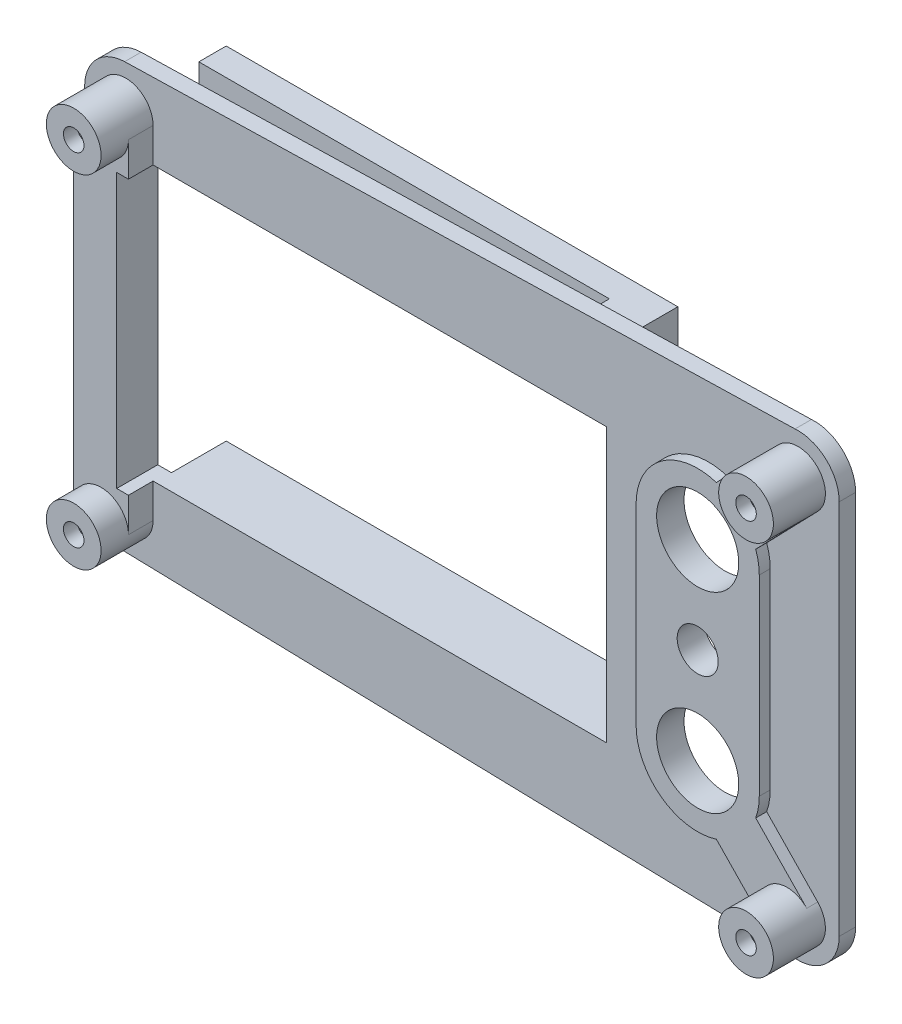
SolidWorks part; units mm, degrees
ref_plane "前视基准面" through (0, 0, 0) normal (0, 0, 1) x (1, 0, 0)
ref_plane "上视基准面" through (0, 0, 0) normal (0, 1, 0) x (1, 0, 0)
ref_plane "右视基准面" through (0, 0, 0) normal (1, 0, 0) x (0, 0, -1)
sketch "草图2" plane through (0, 0, 0) normal (0, 0, 1) x (1, 0, 0)
  line L4 (-49.1276, -26.25) -> (-49.1276, -1.25) construction
  line L7 (-51.1276, -26.25) -> (-51.1276, -1.25)
  line L10 (-47.1276, -26.25) -> (-47.1276, -1.25)
  line L13 (0, -27.5) -> (-6.533, -20.75) construction
  line L16 (-1.4371, -28.8909) -> (-7.9701, -22.1409)
  line L17 (-49.2041, 1.749) -> (-0.2201, 2.999)
  line L19 (1.4371, -26.1091) -> (-5.0959, -19.3591)
  line L21 (-49.2041, -29.249) -> (-0.2201, -30.499)
  line L22 (-6.533, -6.75) -> (0, 0) construction
  line L24 (-52.1276, -1.25) -> (-52.1276, -26.25)
  line L25 (-7.9701, -5.3591) -> (-1.4371, 1.3909)
  line L26 (3.0071, 0) -> (3.0071, -27.5)
  line L28 (-5.0959, -8.1409) -> (1.4371, -1.3909)
  line L41 (-47.9841, -13.75) -> (-47.9841, -3.75)
  line L42 (-13.9841, -13.75) -> (-13.9841, -3.75)
  line L43 (-47.9841, -3.75) -> (-13.9841, -3.75)
  line L45 (-13.9841, -13.75) -> (-13.9841, -23.75)
  line L46 (-47.9841, -13.75) -> (-47.9841, -23.75)
  line L47 (-13.9841, -23.75) -> (-47.9841, -23.75)
  line L48 (-6.533, -6.75) -> (-6.533, -20.75) construction
  line L49 (-2.033, -6.75) -> (-2.033, -20.75)
  line L50 (-11.033, -6.75) -> (-11.033, -20.75)
  circle A0 centre (0, 0) radius 0.75
  circle A1 centre (0, 0) radius 1.5
  circle A2 centre (0, -27.5) radius 0.75
  circle A3 centre (0, -27.5) radius 2
  circle A4 centre (-49.1276, -26.25) radius 0.75
  circle A5 centre (-49.1276, -26.25) radius 2
  circle A6 centre (-49.1276, -1.25) radius 0.75
  circle A7 centre (-49.1276, -1.25) radius 2
  circle A26 centre (-6.533, -13.75) radius 1.5
  circle A28 centre (-6.533, -6.75) radius 3
  circle A29 centre (-6.533, -20.75) radius 3
  arc A30 (-2.033, -6.75) -> (-11.033, -6.75) centre (-6.533, -6.75) ccw
  arc A31 (-11.033, -20.75) -> (-2.033, -20.75) centre (-6.533, -20.75) ccw
  arc A33 (3.0071, 0) -> (-0.2201, 2.999) centre (0, 0) ccw
  circle A34 centre (-49.1276, -1.25) radius 1.5
  arc A35 (-0.2201, -30.499) -> (3.0071, -27.5) centre (0, -27.5) ccw
  arc A36 (-49.2041, 1.749) -> (-52.1276, -1.25) centre (-49.1276, -1.25) ccw
  arc A37 (-52.1276, -26.25) -> (-49.2041, -29.249) centre (-49.1276, -26.25) ccw
  circle A38 centre (-49.1276, -26.25) radius 1.5
  circle A39 centre (0, -27.5) radius 1.5
  circle A40 centre (0, 0) radius 1.5
  circle A41 centre (0, 0) radius 2
  arc A42 (-51.1276, -26.25) -> (-47.1276, -26.25) centre (-49.1276, -26.25) ccw
  arc A43 (-47.1276, -1.25) -> (-51.1276, -1.25) centre (-49.1276, -1.25) ccw
  arc A44 (-1.4371, -28.8909) -> (1.4371, -26.1091) centre (0, -27.5) ccw
  arc A45 (-5.0959, -19.3591) -> (-7.9701, -22.1409) centre (-6.533, -20.75) ccw
  arc A46 (-7.9701, -5.3591) -> (-5.0959, -8.1409) centre (-6.533, -6.75) ccw
  arc A47 (1.4371, -1.3909) -> (-1.4371, 1.3909) centre (0, 0) ccw
  point P12 (-24.492, -0.625)
  point P18 (-49.1276, -13.75)
  point P19 (-48.9841, -13.75)
  point P24 (-24.492, -26.875)
  point P26 (-3.2665, -24.125)
  point P29 (0, -13.75)
  point P33 (-3.2665, -3.375)
  point P39 (-24.492, -0.625)
  point P46 (-24.492, -26.875)
  point P51 (-48.9841, -13.75)
  point P58 (0, -13.75)
  point P75 (-6.533, -13.75)
  dimension "D2" = 1.5
  dimension "D3" = 4
  dimension "D7" = 10
  dimension "D10" = 6
  dimension "D11" = 3
  dimension "D5" = 27.5
  dimension "D8" = 10
  dimension "D9" = 7
  dimension "D12" = 34
extrude "凸台-拉伸1" add sketch "草图2" along normal blind 1.2 contours L24 A37 L21 A35 L26 A33 L17 A36 L45 L47 L46 L41 L43 L42 A1 A3 A5 A7 A31 L50 A30 L49 region at (-24.6956, 1.729, 0)
extrude "凸台-拉伸7" add sketch "草图2<8>" along normal blind 2 contours L50 A31 L49 A30 A28 A26 A29 region at (-9.0426, -24.1837, 0)
sketch "草图2<8>" plane through (0, 0, 0) normal (0, 0, 1) x (1, 0, 0) same geometry as "草图2"
extrude "凸台-拉伸8" add sketch "草图2<9>" along normal blind 5 contours A7 A34 region at (-49.1276, 0.6934, 0)
sketch "草图2<9>" plane through (0, 0, 0) normal (0, 0, 1) x (1, 0, 0) same geometry as "草图2"
extrude "凸台-拉伸9" add sketch "草图2<10>" along normal blind 5 contours A3 A39 region at (-1.3516, -26.1035, 0)
sketch "草图2<10>" plane through (0, 0, 0) normal (0, 0, 1) x (1, 0, 0) same geometry as "草图2"
extrude "凸台-拉伸10" add sketch "草图2<11>" along normal blind 5 contours A41 A1 region at (0.729, 1.8015, 0)
sketch "草图2<11>" plane through (0, 0, 0) normal (0, 0, 1) x (1, 0, 0) same geometry as "草图2"
extrude "凸台-拉伸11" add sketch "草图2<12>" along normal blind 5 contours A5 A38 region at (-49.1276, -24.3066, 0)
sketch "草图2<12>" plane through (0, 0, 0) normal (0, 0, 1) x (1, 0, 0) same geometry as "草图2"
extrude "凸台-拉伸12" add sketch "草图2<13>" along normal blind 5 contours A34 A6 region at (-50.5852, -1.25, 0)
sketch "草图2<13>" plane through (0, 0, 0) normal (0, 0, 1) x (1, 0, 0) same geometry as "草图2"
extrude "凸台-拉伸13" add sketch "草图2<14>" along normal blind 5 contours A38 A4 region at (-50.5852, -26.25, 0)
sketch "草图2<14>" plane through (0, 0, 0) normal (0, 0, 1) x (1, 0, 0) same geometry as "草图2"
extrude "凸台-拉伸14" add sketch "草图2<15>" along normal blind 5 contours A1 A0 region at (-1.4576, 0, 0)
sketch "草图2<15>" plane through (0, 0, 0) normal (0, 0, 1) x (1, 0, 0) same geometry as "草图2"
extrude "凸台-拉伸15" add sketch "草图2<16>" along normal blind 5 contours A39 A2 region at (-1.4576, -27.5, 0)
sketch "草图2<16>" plane through (0, 0, 0) normal (0, 0, 1) x (1, 0, 0) same geometry as "草图2"
extrude "切除-拉伸4" cut sketch "草图2<19>" along normal blind 4 contours A34 A6 region at (-50.5852, -1.25, 0)
sketch "草图2<19>" plane through (0, 0, 0) normal (0, 0, 1) x (1, 0, 0) same geometry as "草图2"
extrude "切除-拉伸5" cut sketch "草图2<20>" along normal blind 4 contours A38 A4 region at (-50.5852, -26.25, 0)
sketch "草图2<20>" plane through (0, 0, 0) normal (0, 0, 1) x (1, 0, 0) same geometry as "草图2"
extrude "切除-拉伸6" cut sketch "草图2<21>" along normal blind 4 contours A39 A2 region at (-1.4576, -27.5, 0)
sketch "草图2<21>" plane through (0, 0, 0) normal (0, 0, 1) x (1, 0, 0) same geometry as "草图2"
extrude "切除-拉伸7" cut sketch "草图2<22>" along normal blind 4 contours A1 A0 region at (-1.4576, 0, 0)
sketch "草图2<22>" plane through (0, 0, 0) normal (0, 0, 1) x (1, 0, 0) same geometry as "草图2"
extrude "凸台-拉伸16" add sketch "草图2<23>" along normal blind 3 contours A7 L7 A5 L10 L47 L46 L41 L43 region at (-49.5105, -13.75, 0)
sketch "草图2<23>" plane through (0, 0, 0) normal (0, 0, 1) x (1, 0, 0) same geometry as "草图2"
extrude "凸台-拉伸18" add sketch "草图2<24>" along normal blind 2 contours A31 L16 A3 L19 | L16 A31 L19 A29 | L28 A30 L25 A28 | A41 L25 A30 L28 region at (-2.2831, -25.1411, 0) region at (-4.0683, -23.2966, 0) region at (-4.0683, -4.2034, 0) region at (-2.2831, -2.3589, 0)
sketch "草图2<24>" plane through (0, 0, 0) normal (0, 0, 1) x (1, 0, 0) same geometry as "草图2"
sketch "草图3" plane through (0, 0, 0) normal (0, 0, -1) x (-1, 0, 0)
  line L1 (13.9841, -23.75) -> (46.9841, -23.75)
  line L2 (13.9841, -23.75) -> (13.9841, -28.75)
  line L3 (13.9841, -28.75) -> (46.9841, -28.75)
  line L4 (46.9841, -23.75) -> (46.9841, -28.75)
  line L5 (13.9841, -3.75) -> (46.9841, -3.75)
  line L6 (13.9841, -3.75) -> (13.9841, 1.25)
  line L7 (13.9841, 1.25) -> (46.9841, 1.25)
  line L8 (46.9841, -3.75) -> (46.9841, 1.25)
  dimension "D1" = 33
  dimension "D2" = 33
  dimension "D3" = 5
  dimension "D4" = 5
extrude "凸台-拉伸21" add sketch "草图3" along normal blind 4
sketch "草图4" plane through (0, -28.75, 0) normal (0, -1, 0) x (1, 0, 0)
  line L1 (-46.9841, 0) -> (-16.9841, 0)
  line L2 (-46.9841, 0) -> (-46.9841, -2)
  line L3 (-46.9841, -2) -> (-16.9841, -2)
  line L4 (-16.9841, 0) -> (-16.9841, -2)
  dimension "D1" = 30
  dimension "D2" = 2
extrude "切除-拉伸9" cut sketch "草图4" against normal blind 2
sketch "草图5" plane through (0, 1.25, 0) normal (0, 1, 0) x (1, 0, 0)
  line L1 (-46.9841, 0) -> (-16.9841, 0)
  line L2 (-46.9841, 0) -> (-46.9841, 2)
  line L3 (-46.9841, 2) -> (-16.9841, 2)
  line L4 (-16.9841, 0) -> (-16.9841, 2)
  dimension "D1" = 30
  dimension "D2" = 2
extrude "切除-拉伸10" cut sketch "草图5" against normal blind 2
